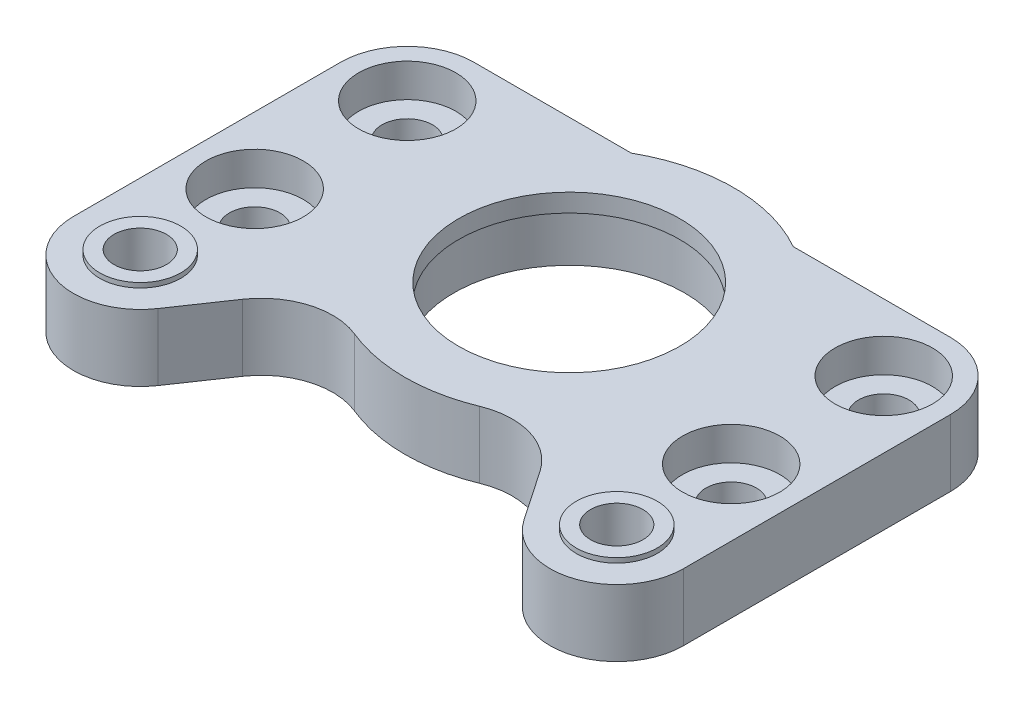
SolidWorks part; units mm, degrees
ref_plane "前视基准面" through (0, 0, 0) normal (0, 0, 1) x (1, 0, 0)
ref_plane "上视基准面" through (0, 0, 0) normal (0, 1, 0) x (1, 0, 0)
ref_plane "右视基准面" through (0, 0, 0) normal (1, 0, 0) x (0, 0, -1)
sketch "草图1" plane through (0, 0, 0) normal (0, 1, 0) x (1, 0, 0)
  line L0 (31.9858, -42) -> (31.9858, 0) construction
  line L1 (7, 0) -> (23.4915, 0)
  line L2 (0, -7) -> (0, -35)
  line L4 (63.9716, -7) -> (63.9716, -35)
  line L5 (40.4802, 0) -> (56.9716, 0)
  line L6 (63.9716, -29.0907) -> (63.9716, -48.7588) construction
  line L7 (50.4643, -37.8804) -> (61.4436, -54.0056) construction
  line L8 (47.5904, -33.6595) -> (51.1855, -38.9396)
  line L9 (16.3812, -33.6595) -> (12.7861, -38.9396)
  line L10 (53.2692, -42) -> (56.9716, -42)
  arc A0 (0, -35) -> (12.7861, -38.9396) centre (7, -35) ccw
  circle A1 centre (7, -35) radius 2.75
  arc A2 (7, 0) -> (0, -7) centre (7, -7) ccw
  circle A3 centre (7, -7) radius 2.65
  circle A4 centre (7, -23) radius 2.65
  circle A5 centre (56.9716, -35) radius 2.75
  arc A6 (63.9716, -35) -> (51.1855, -38.9396) centre (56.9716, -35) cw
  circle A7 centre (56.9716, -23) radius 2.65
  circle A8 centre (56.9716, -7) radius 2.65
  arc A9 (56.9716, 0) -> (63.9716, -7) centre (56.9716, -7) cw
  circle A10 centre (31.9858, -15) radius 12.1
  arc A11 (25.4321, -30.9437) -> (38.5396, -30.9437) centre (31.9858, -15) ccw
  arc A12 (47.5904, -33.6595) -> (38.5396, -30.9437) centre (41.391, -37.8805) ccw
  arc A13 (16.3812, -33.6595) -> (25.4321, -30.9437) centre (22.5807, -37.8805) cw
  arc A14 (40.4802, 0) -> (23.4915, 0) centre (31.9858, -15) ccw
  dimension "D3" = 14
  dimension "D4" = 5.5
  dimension "D5" = 14
  dimension "D6" = 5.3
  dimension "D1" = 24.2
  dimension "D9" = 34.4763
  dimension "D11" = 15
  dimension "D2" = 15
  dimension "D7" = 16
  dimension "D10" = 34.25
extrude "凸台-拉伸1" add sketch "草图1" along normal blind 7 contours L5 A14 L1 A2 L2 A0 L9 A13 A11 A12 L8 A6 L4 A9 A8 A5 A4 A3 A1 A7 A10 region at (15.2457, 0, 0.7778)
sketch "草图2" plane through (0, 0, 0) normal (0, -1, 0) x (1, 0, 0)
  circle A0 centre (31.9858, 15) radius 12.1 construction
  circle A1 centre (31.9858, 15) radius 12.1
  circle A2 centre (31.9858, 15) radius 11.6
  dimension "D1" = 0.5
extrude "凸台-拉伸2" add sketch "草图2" along normal blind 1.9 from surface starting at face at (56.9716, 7, 9.65)
sketch "草图3" plane through (0, 7, 0) normal (0, 1, 0) x (1, 0, 0)
  line L0 (31.9858, -15) -> (31.9858, -9.3775) construction
  circle A0 centre (56.9716, -7) radius 5.1
  circle A1 centre (56.9716, -23) radius 2.65 construction
  circle A2 centre (56.9716, -7) radius 2.65 construction
  circle A3 centre (56.9716, -23) radius 2.65
  circle A4 centre (56.9716, -7) radius 2.65
  circle A5 centre (56.9716, -23) radius 5.1
  circle A6 centre (7, -7) radius 2.65
  circle A7 centre (7, -23) radius 2.65
  circle A8 centre (7, -23) radius 5.1
  circle A9 centre (7, -7) radius 5.1
  dimension "D1" = 10.2
extrude "切除-拉伸1" cut sketch "草图3" against normal blind 3.5 contours A6 | A9 | A8 | A5 | A0
sketch "草图4" plane through (0, 7, 0) normal (0, 1, 0) x (1, 0, 0)
  circle A0 centre (7, -35) radius 4.25
  circle A1 centre (56.9716, -35) radius 4.25
  circle A2 centre (56.9716, -35) radius 2.75 construction
  circle A3 centre (7, -35) radius 2.75 construction
  circle A4 centre (56.9716, -35) radius 2.75
  circle A5 centre (7, -35) radius 2.75
  dimension "D1" = 8.5
extrude "凸台-拉伸3" add sketch "草图4" along normal blind 0.5
ref_axis "基准轴1" through (7, 7.5, 35) along (0, -1, 0)
ref_plane "基准面1" through (0, 0, 35) normal (0, 0, 1) x (1, 0, 0)
sketch "草图5" plane through (0, 0, 35) normal (0, 0, 1) x (1, 0, 0)
  line L0 (7, 0) -> (7, 7.5) construction
  line L1 (12, 0) -> (9.65, 3.5)
  line L2 (9.65, 0) -> (9.65, 3.5) construction
  line L3 (7, 0) -> (12, 0)
  line L4 (7, 0) -> (23.4915, 0) construction
  line L5 (9.65, 3.5) -> (7, 3.5)
  line L6 (7, 3.5) -> (7, 0)
  dimension "D1" = 3.5
  dimension "D2" = 5
revolve "切除-旋转1" cut sketch "草图5" angle 360 about L0
ref_plane "基准面2" through (31.9858, 0, 0) normal (-1, 0, 0) x (0, 0, 1)
mirror "镜向1" about plane through (31.9858, 0, 0) normal (-1, 0, 0) of "切除-旋转1"
